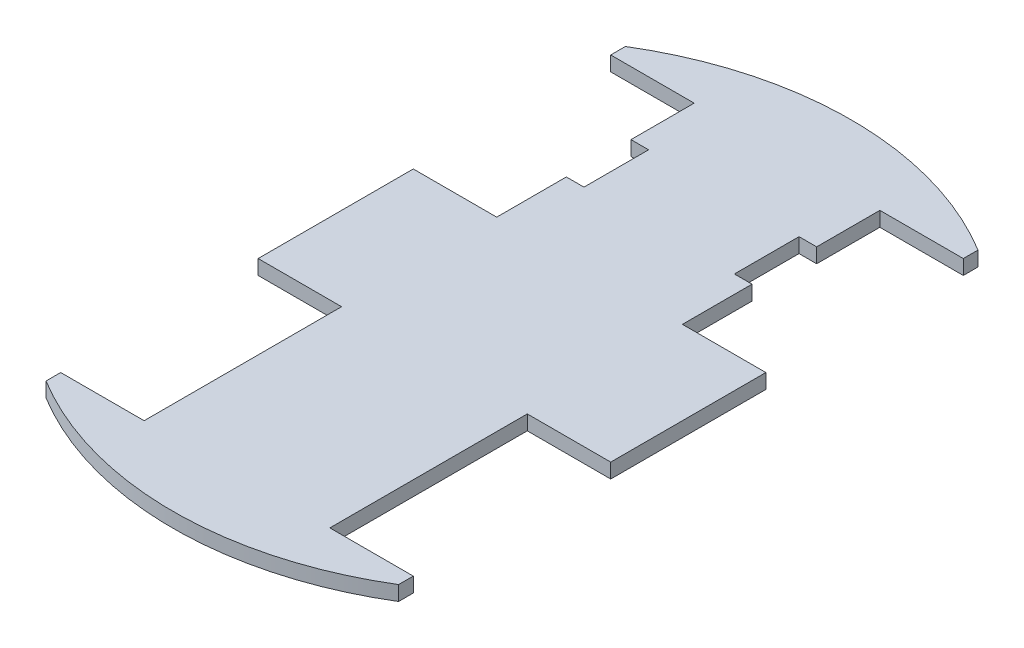
SolidWorks part; units mm, degrees
material "Oak"
ref_plane "Front Plane" through (0, 0, 0) normal (0, 0, 1) x (1, 0, 0)
ref_plane "Top Plane" through (0, 0, 0) normal (0, 1, 0) x (1, 0, 0)
ref_plane "Right Plane" through (0, 0, 0) normal (1, 0, 0) x (0, 0, -1)
sketch "Sketch1" plane through (0, 0, 0) normal (0, 1, 0) x (1, 0, 0)
  line L0 (50.292, 32.512) -> (76.2, 32.512) construction
  line L1 (-76.2, 32.512) -> (-50.292, 32.512) construction
  line L2 (-76.2, 32.512) -> (-76.2, -32.512) construction
  line L3 (-76.2, -32.512) -> (-50.292, -32.512) construction
  line L4 (-50.292, 32.512) -> (-50.292, -32.512) construction
  line L5 (-76.2, 32.512) -> (-50.292, -32.512) construction
  line L6 (-76.2, -32.512) -> (-50.292, 32.512) construction
  line L7 (50.292, 32.512) -> (50.292, -32.512) construction
  line L8 (50.292, -32.512) -> (76.2, -32.512) construction
  line L9 (76.2, 32.512) -> (76.2, -32.512) construction
  line L10 (50.292, 32.512) -> (76.2, -32.512) construction
  line L11 (50.292, -32.512) -> (76.2, 32.512) construction
  line L12 (-76.2, -119.888) -> (-50.292, -119.888) construction
  line L13 (-76.2, -119.888) -> (-76.2, -184.912) construction
  line L14 (-76.2, -184.912) -> (-50.292, -184.912) construction
  line L15 (-50.292, -119.888) -> (-50.292, -184.912) construction
  line L16 (-76.2, -119.888) -> (-50.292, -184.912) construction
  line L17 (-76.2, -184.912) -> (-50.292, -119.888) construction
  line L18 (50.292, -119.888) -> (76.2, -119.888) construction
  line L19 (50.292, -119.888) -> (50.292, -184.912) construction
  line L20 (50.292, -184.912) -> (76.2, -184.912) construction
  line L21 (76.2, -119.888) -> (76.2, -184.912) construction
  line L22 (50.292, -119.888) -> (76.2, -184.912) construction
  line L23 (50.292, -184.912) -> (76.2, -119.888) construction
  line L24 (-76.2, -42.672) -> (-40.132, -42.672)
  line L25 (-76.2, 0) -> (76.2, 0) construction
  line L26 (-76.2, 0) -> (-76.2, -152.4) construction
  line L27 (-76.2, -152.4) -> (76.2, -152.4) construction
  line L28 (76.2, 0) -> (76.2, -152.4) construction
  line L29 (-76.2, 0) -> (76.2, -152.4) construction
  line L30 (-76.2, -152.4) -> (76.2, 0) construction
  line L31 (-40.132, 42.672) -> (-40.132, -42.672)
  line L32 (-76.2, 42.672) -> (-40.132, 42.672)
  line L33 (40.132, -42.672) -> (76.2, -42.672)
  line L34 (40.132, 42.672) -> (40.132, -42.672)
  line L35 (40.132, 42.672) -> (76.2, 42.672)
  line L36 (40.132, -195.072) -> (76.2, -195.072)
  line L37 (40.132, -109.728) -> (40.132, -195.072)
  line L38 (40.132, -109.728) -> (76.2, -109.728)
  line L39 (-76.2, -195.072) -> (-40.132, -195.072)
  line L40 (-40.132, -109.728) -> (-40.132, -195.072)
  line L41 (-76.2, -109.728) -> (-40.132, -109.728)
  line L42 (-76.2, -109.728) -> (-76.2, -42.672)
  line L43 (76.2, -42.672) -> (76.2, -109.728)
  line L44 (-76.2, 42.672) -> (-76.2, 49.022)
  line L45 (76.2, 42.672) -> (76.2, 49.022)
  line L46 (-76.2, -195.072) -> (-76.2, -201.422)
  line L47 (76.2, -195.072) -> (76.2, -201.422)
  line L48 (0, 0) -> (0, 19.7922) construction
  line L49 (-32.512, 15.3535) -> (-40.132, 15.3535)
  line L50 (-32.512, 15.3535) -> (-32.512, -12.5865)
  line L51 (-32.512, -12.5865) -> (-40.132, -12.5865)
  line L52 (-40.132, 15.3535) -> (-40.132, -12.5865)
  line L53 (-32.512, 15.3535) -> (-40.132, -12.5865) construction
  line L54 (-32.512, -12.5865) -> (-40.132, 15.3535) construction
  line L55 (32.512, -12.5865) -> (40.132, -12.5865)
  line L56 (32.512, 15.3535) -> (32.512, -12.5865)
  line L57 (32.512, 15.3535) -> (40.132, 15.3535)
  arc A0 (-76.2, 49.022) -> (76.2, 49.022) centre (0, -76.2) cw
  arc A1 (-76.2, -201.422) -> (76.2, -201.422) centre (0, -76.2) ccw
  point P4 (-63.246, 0)
  point P9 (63.246, 0)
  point P14 (-63.246, -152.4)
  point P19 (63.246, -152.4)
  point P24 (0, -76.2)
  point P52 (-36.322, 1.3835)
  dimension "D7" = 6.35
  dimension "D8" = 7.62
  dimension "D1" = 152.4
  dimension "D2" = 152.4
  dimension "D3" = 25.908
  dimension "D4" = 65.024
  dimension "D6" = 10.16
  dimension "D9" = 27.94
  dimension "D5" = 10.16
extrude "Chassis" add sketch "Sketch1" along normal blind 6.35 contours L46 A1 L47 L36 L37 L38 L43 L33 L34 L55 L56 L57 L35 L45 A0 L44 L32 L31 L49 L50 L51 L24 L42 L41 L40 L39 region at (0, 0, 77.3072)
